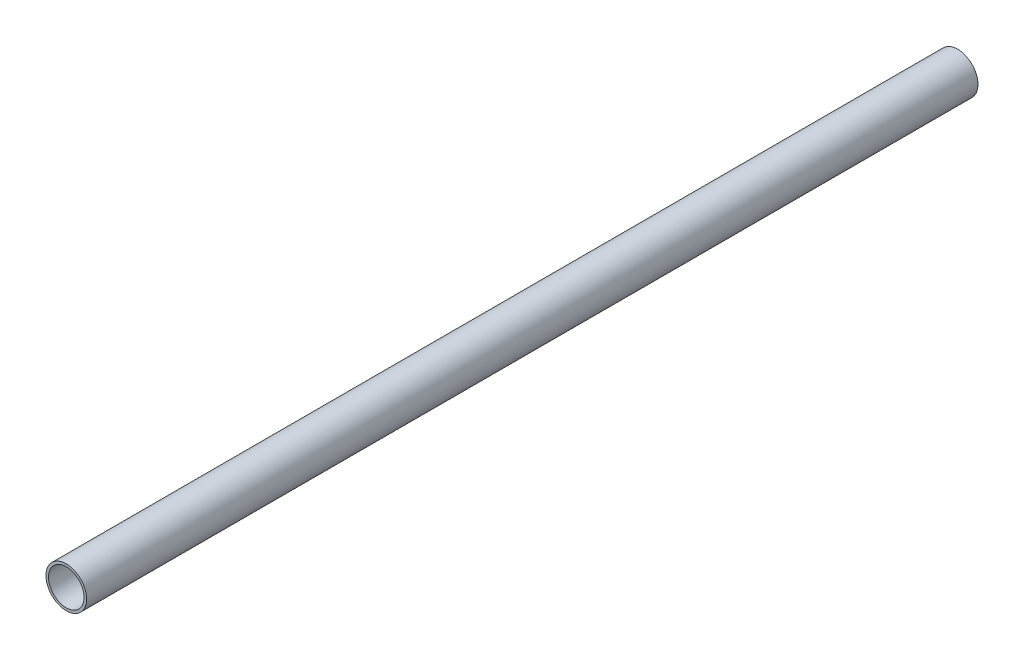
SolidWorks part; units mm, degrees
material "PC High Viscosity"
ref_plane "Front Plane" through (0, 0, 0) normal (0, 0, 1) x (1, 0, 0)
ref_plane "Top Plane" through (0, 0, 0) normal (0, 1, 0) x (1, 0, 0)
ref_plane "Right Plane" through (0, 0, 0) normal (1, 0, 0) x (0, 0, -1)
sketch "Sketch2" plane through (0, 0, 0) normal (0, 0, 1) x (1, 0, 0)
  circle A0 centre (0, 0) radius 11.1125
  circle A1 centre (0, 0) radius 12.7
  dimension "D1" = 25.4
  dimension "D2" = 22.225
extrude "Boss-Extrude1" add sketch "Sketch2" along normal mid plane 556.85
